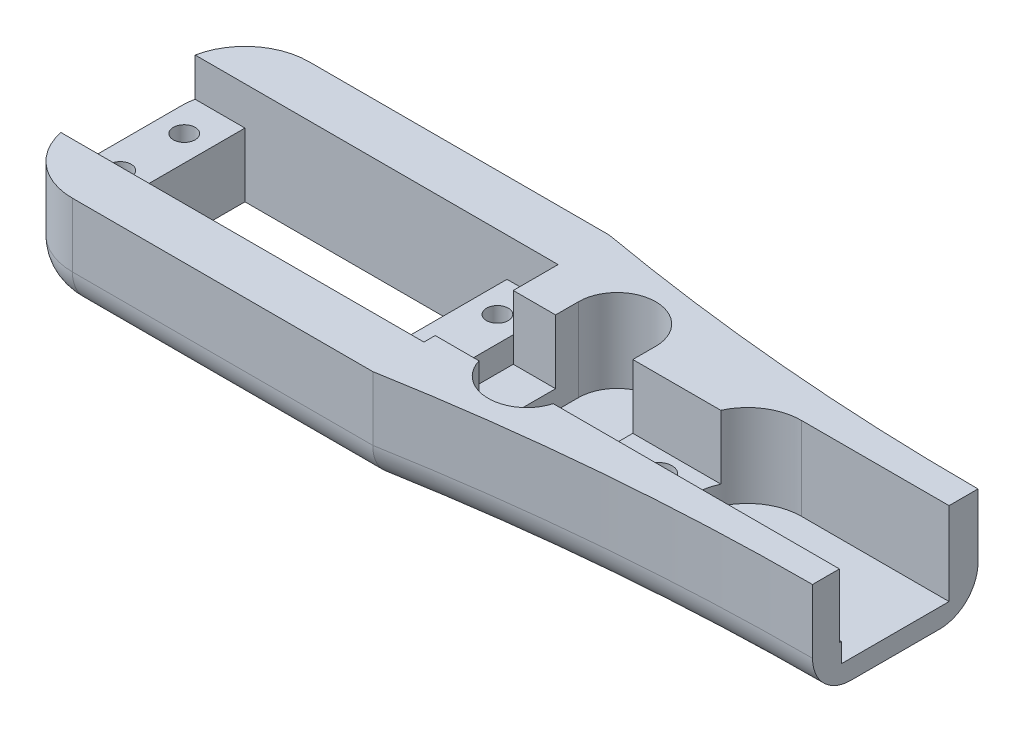
SolidWorks part; units mm, degrees
ref_plane "Front Plane" through (0, 0, 0) normal (0, 0, 1) x (1, 0, 0)
ref_plane "Top Plane" through (0, 0, 0) normal (0, 1, 0) x (1, 0, 0)
ref_plane "Right Plane" through (0, 0, 0) normal (1, 0, 0) x (0, 0, -1)
sketch "Sketch1" plane through (0, 0, 0) normal (0, 1, 0) x (1, 0, 0)
  line L0 (-42.5547, 14.2429) -> (-42.5547, -6.7571)
  line L1 (-42.5547, -6.7571) -> (-1.5547, -6.7571)
  line L2 (-1.5547, -6.7571) -> (-1.5547, 14.2429)
  line L3 (-1.5547, 14.2429) -> (-42.5547, 14.2429)
  line L4 (-50.5547, 22.2429) -> (-50.5547, -14.7571)
  line L5 (-50.5547, -14.7571) -> (6.4453, -14.7571)
  line L6 (6.4453, -14.7571) -> (6.4453, 22.2429)
  line L7 (6.4453, 22.2429) -> (-50.5547, 22.2429)
  line L8 (6.4453, 3.7429) -> (-22.0547, 3.7429)
  line L11 (-22.0547, 3.7429) -> (6.4453, 3.7429)
  line L12 (132.9453, 22.2429) -> (132.9453, -14.7571)
  circle A0 centre (2.4453, 8.7429) radius 1.7
  circle A1 centre (2.4453, -1.2571) radius 1.7
  circle A2 centre (-46.5547, -1.2571) radius 1.7
  circle A3 centre (-46.5547, 8.7429) radius 1.7
  arc A4 (6.4453, 22.2429) -> (132.9453, 22.2429) centre (69.6953, 379.6894) ccw
  arc A5 (6.4453, -14.7571) -> (132.9453, -14.7571) centre (69.6953, -372.2036) cw
  point P22 (132.9453, 3.7429)
  dimension "D4" = 3.4
  dimension "D1" = 8
  dimension "D2" = 21
  dimension "D3" = 41
extrude "Boss-Extrude1" add sketch "Sketch1" along normal blind 16 contours L6 A5 L12 A4 | L6 L2 L1 L0 L3 L7 L4 L5 A2 A1 A0 A3 region at (5.7657, 0, 5.5071) region at (69.6953, 0, -3.7429)
sketch "Sketch2" plane through (0, 16, 0) normal (0, 1, 0) x (1, 0, 0)
  line L8 (-22.0547, -6.7571) -> (-22.0547, -2.3508)
  line L9 (-42.5547, -6.7571) -> (-1.5547, -6.7571) construction
  line L10 (6.4453, -6.7571) -> (-50.5547, -6.7571)
  line L11 (-50.5547, 22.2429) -> (-50.5547, -14.7571) construction
  line L12 (-42.5547, 3.7429) -> (-38.9164, 3.7429)
  line L13 (-42.5547, 14.2429) -> (-42.5547, -6.7571) construction
  line L14 (6.4453, 14.2429) -> (-50.5547, 14.2429)
  line L15 (-50.5547, -6.7571) -> (-50.5547, 14.2429)
  line L16 (6.4453, 14.2429) -> (6.4453, -6.7571)
  line M6 (-50.5547, 22.2429) -> (-50.5547, -14.7571)
  line M10 (-42.5547, 14.2429) -> (-1.5547, 14.2429)
  line M11 (-1.5547, 14.2429) -> (-1.5547, -6.7571)
  line M12 (-1.5547, -6.7571) -> (-42.5547, -6.7571)
  line M13 (-42.5547, -6.7571) -> (-42.5547, 14.2429)
  circle M14 centre (-46.5547, -1.2571) radius 1.7
  circle M15 centre (2.4453, -1.2571) radius 1.7
  circle M16 centre (2.4453, 8.7429) radius 1.7
  circle M17 centre (-46.5547, 8.7429) radius 1.7
extrude "Cut-Extrude1" cut sketch "Sketch2" against normal blind 6 contours M10 M13 M12 M11 | L14 L10 M13 M6 M17 M14 | L16 L14 L10 M11 M16 M15 region at (2.4453, 16, -3.7429) region at (-22.0547, 16, -3.7429) region at (-46.5547, 16, -3.7429)
sketch "Sketch3" plane through (0, 16, 0) normal (0, 1, 0) x (1, 0, 0)
  line L0 (132.9453, -8.2571) -> (132.9453, 15.7429)
  line L1 (132.9453, 22.2429) -> (132.9453, -14.7571) construction
  line L2 (105.9453, 3.7429) -> (105.9453, 15.7429)
  line L3 (105.9453, 3.7429) -> (105.9453, -8.2571)
  line L4 (105.9453, -8.2571) -> (132.9453, -8.2571)
  line L6 (132.9453, 15.7429) -> (105.9453, 15.7429)
  line L7 (105.9453, 15.7429) -> (122.4453, 15.7429)
  line L8 (127.4453, 15.7429) -> (127.4453, 23.7526)
  line L9 (127.4453, 23.7526) -> (122.4453, 23.7526)
  line L10 (122.4453, 23.7526) -> (122.4453, 15.7429)
  line L11 (122.4453, 15.7429) -> (127.4453, 15.7429)
  line L12 (132.9453, 3.7429) -> (129.8323, 3.7429)
  line L13 (122.4453, -8.2571) -> (127.4453, -8.2571)
  line L14 (122.4453, -16.2668) -> (122.4453, -8.2571)
  line L15 (127.4453, -16.2668) -> (122.4453, -16.2668)
  line L16 (127.4453, -8.2571) -> (127.4453, -16.2668)
  arc M12 (6.4453, -14.7571) -> (132.9453, -14.7571) centre (69.6953, -372.2036) cw
  line M13 (132.9453, -14.7571) -> (132.9453, 22.2429)
  arc M14 (132.9453, 22.2429) -> (6.4453, 22.2429) centre (69.6953, 379.6894) cw
  dimension "D1" = 27
extrude "Cut-Extrude3" cut sketch "Sketch3" against normal blind 13 contours L10 L6 L8 M14 | L16 L4 L14 M12 | L0 L6 L7 L2 L3 L4 M13 region at (119.4453, 16, -3.7429) region at (125.0072, 16, 10.8516) region at (125.0072, 16, -18.3373)
ref_plane "Plane1" through (0, 106, 0) normal (0, 1, 0) x (1, 0, 0)
fillet "Fillet3" radius 10 2 edges at (-50.5547, 8, 14.7571) (-50.5547, 8, -22.2429)
sketch "Sketch4" plane through (0, 106, 0) normal (0, 1, 0) x (1, 0, 0)
  line L0 (18.0294, 20.3856) -> (18.0294, -12.8998)
  line L1 (132.9453, 22.2429) -> (132.9453, -14.7571)
  arc A0 (6.4453, 22.2429) -> (122.4453, 20.5432) centre (69.6953, 379.6894) ccw construction
  arc A1 (122.4453, -13.0574) -> (6.4453, -14.7571) centre (69.6953, -372.2036) ccw construction
  arc A2 (18.0294, -12.8998) -> (132.9453, -14.7571) centre (69.6953, -372.2036) cw
  arc A3 (18.0294, 20.3856) -> (132.9453, 22.2429) centre (69.6953, 379.6894) ccw
ref_plane "Plane2" through (0, 16, 0) normal (0, 1, 0) x (1, 0, 0)
extrude "Boss-Extrude2" add sketch "Sketch4" along normal blind 7 separate body
fillet "Fillet1" radius 10 4 edges at (132.9453, 113, -3.7429) (75.5613, 113, 9.2516) (18.0294, 113, -3.7429) (75.5613, 113, -16.7374)
fillet "Fillet2" radius 10 rebuild error yes
sketch "Sketch10" plane through (0, 113, 0) normal (0, 1, 0) x (1, 0, 0)
  line L0 (27.5688, 3.7429) -> (95.1334, 3.7429)
  line L1 (27.5688, 9.5401) -> (27.5688, -2.0543) construction
  circle A0 centre (32.6164, 3.7429) radius 2.15
  circle A1 centre (95.1334, 3.7429) radius 2.15
  dimension "D1" = 4.3
  dimension "D2" = 4.3
extrude "Cut-Extrude7" cut sketch "Sketch10" against normal blind 125 contours A0 | A1
ref_plane "Plane4" through (0, 0, 100) normal (0, 0, 1) x (1, 0, 0)
sketch "Sketch12" plane through (0, 0, 100) normal (0, 0, 1) x (1, 0, 0)
  line L1 (-2.3162, 127.0375) -> (154.8575, 127.0375)
  line L2 (-2.3162, 127.0375) -> (-2.3162, 74.9287)
  line L3 (-2.3162, 74.9287) -> (154.8575, 74.9287)
  line L4 (154.8575, 127.0375) -> (154.8575, 74.9287)
extrude "Cut-Extrude10" cut sketch "Sketch12" against normal blind 145
sketch "Sketch13" plane through (0, 16, 0) normal (0, 1, 0) x (1, 0, 0)
  line L0 (95.1334, 3.7429) -> (32.6164, 3.7429)
  line L1 (81.1611, 3.7429) -> (46.5886, 3.7429) construction
  line L2 (81.1611, -4.677) -> (46.5886, -4.677)
  line L3 (81.1611, 12.1628) -> (46.5886, 12.1628)
  arc A0 (81.1611, -4.677) -> (81.1611, 12.1628) centre (81.1611, 3.7429) ccw
  arc A1 (46.5886, 12.1628) -> (46.5886, -4.677) centre (46.5886, 3.7429) ccw
  point P6 (63.8749, 3.7429)
extrude "Cut-Extrude11" cut sketch "Sketch13" against normal blind 13 contours L3 A1 L0 A0 | L0 A1 L2 A0 region at (63.8749, 16, 0.291) region at (63.8749, 16, -7.7767)
sketch "Sketch14" plane through (0, 16, 0) normal (0, 1, 0) x (1, 0, 0)
  line L0 (32.6164, 3.7429) -> (19.1107, 3.7429)
  line L1 (19.1107, 10.8019) -> (19.1107, -3.3161) construction
  line L2 (25.1546, 10.8019) -> (25.1546, -3.3161)
  line L3 (13.0668, 10.8019) -> (13.0668, -3.3161)
  arc A0 (25.1546, 10.8019) -> (13.0668, 10.8019) centre (19.1107, 10.8019) ccw
  arc A1 (13.0668, -3.3161) -> (25.1546, -3.3161) centre (19.1107, -3.3161) ccw
  point P5 (19.1107, 3.7429)
extrude "Cut-Extrude12" cut sketch "Sketch14" against normal blind 13 contours L3 A1 L2 A0 region at (24.866, 16, -7.2724)
fillet "Fillet4" radius 6 7 edges at (-17.0547, 0, -22.2429) (-47.6258, 0, -19.314) (-50.5547, 0, -3.7429) (69.6953, 0, -16.69) (69.6953, 0, 9.2042) (-17.0547, 0, 14.7571) (-47.6258, 0, 11.8282)
sketch "Sketch15" plane through (0, 16, 0) normal (0, 1, 0) x (1, 0, 0)
  line L0 (6.4453, 7.2234) -> (105.9453, 7.2234)
  line L1 (6.4453, 14.2429) -> (6.4453, -6.7571) construction
  line L2 (105.9453, -8.2571) -> (105.9453, 15.7429) construction
  line L3 (105.9453, 7.2234) -> (116.4418, -8.2571)
  line L4 (105.9453, -8.2571) -> (122.4453, -8.2571) construction
  line L5 (116.4418, -8.2571) -> (116.4418, -12.2268)
  line L6 (116.4418, -12.2268) -> (111.5476, -12.2268)
  line L7 (111.5476, -12.2268) -> (109.2027, -12.2268)
  line L8 (109.2027, -12.2268) -> (106.5111, -8.2571)
  line L9 (105.9453, -8.2571) -> (122.4453, -8.2571) construction
  line L10 (106.5111, -8.2571) -> (105.9453, -4.9888)
  line L11 (105.9453, -8.2571) -> (105.9453, 15.7429) construction
  line L12 (105.9453, -4.9888) -> (6.4453, -4.9888)
  line L13 (6.4453, -4.9888) -> (6.4453, 7.2234)
  arc A0 (122.4453, -13.0574) -> (6.4453, -14.7571) centre (69.6953, -372.2036) ccw construction
extrude "Cut-Extrude13" cut sketch "Sketch15" against normal blind 10
sketch "Sketch16" plane through (0, 16, 0) normal (0, 1, 0) x (1, 0, 0)
  line L0 (69.6953, 16.69) -> (69.6953, -16.1354)
  line L1 (69.6953, -16.1354) -> (149.2754, -16.1354)
  line L2 (149.2754, -16.1354) -> (151.2235, 41.0626)
  line L3 (151.2235, 41.0626) -> (69.6953, 41.0626)
  line L4 (69.6953, 41.0626) -> (69.6953, 16.69)
  arc A0 (6.4453, 22.2429) -> (122.4453, 20.5432) centre (69.6953, 379.6894) ccw construction
extrude "Cut-Extrude14" cut sketch "Sketch16" against normal blind 20
